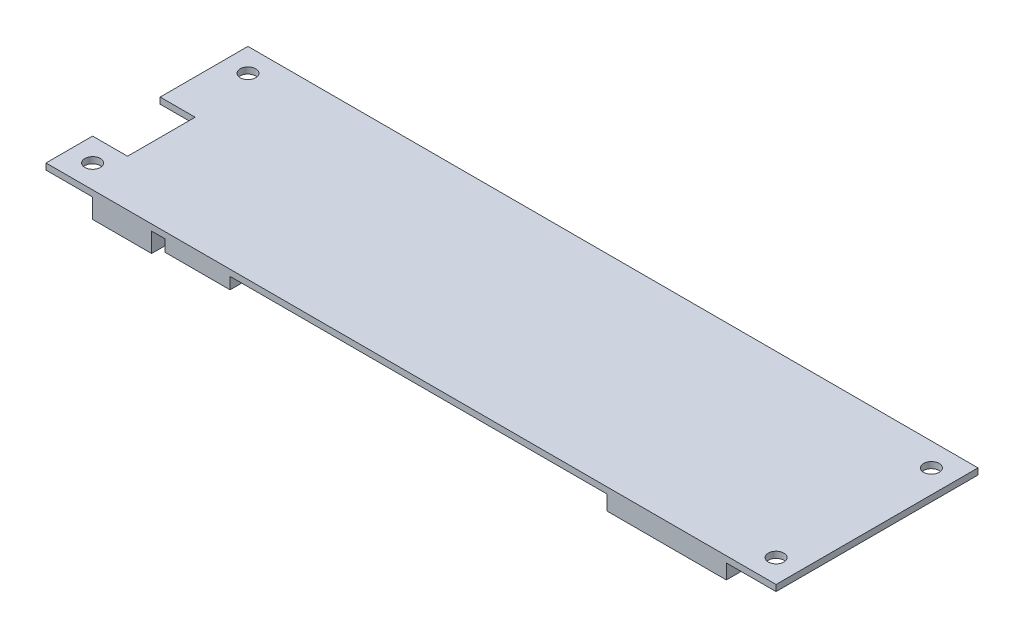
SolidWorks part; units mm, degrees
ref_plane "前视基准面" through (0, 0, 0) normal (0, 0, 1) x (1, 0, 0)
ref_plane "上视基准面" through (0, 0, 0) normal (0, 1, 0) x (1, 0, 0)
ref_plane "右视基准面" through (0, 0, 0) normal (1, 0, 0) x (0, 0, -1)
other "Configuration Table"
sketch "草图1" plane through (0, 0, 0) normal (0, 1, 0) x (1, 0, 0)
  line L1 (-47, -13) -> (47, -13)
  line L2 (-47, -13) -> (-47, 13)
  line L3 (-47, 13) -> (47, 13)
  line L4 (47, -13) -> (47, 13)
  line L5 (-47, -13) -> (47, 13) construction
  line L6 (-47, 13) -> (47, -13) construction
  circle A0 centre (-44, 10) radius 1
  circle A1 centre (-44, -10) radius 1
  circle A2 centre (44, 10) radius 1
  circle A3 centre (44, -10) radius 1
  point P0 (0, 0)
  dimension "D3" = 2
  dimension "D4" = 3
  dimension "D1" = 94
  dimension "D2" = 26
  dimension "D5" = 3
  dimension "D6" = 3
  dimension "D7" = 3
extrude "凸台-拉伸1" add sketch "草图1" along normal blind 0.8
sketch "草图2" plane through (0, 0.8, 0) normal (0, 1, 0) x (1, 0, 0)
  line L0 (-47, 13) -> (-47, -13) construction
  line L1 (-42.2, 3.9) -> (-36.7, 3.9)
  line L2 (-42.2, 3.9) -> (-42.2, -3.9)
  line L3 (-42.2, -3.9) -> (-36.7, -3.9)
  line L4 (-36.7, 3.9) -> (-36.7, -3.9)
  line L5 (40.6, 3.9) -> (46.1, 3.9)
  line L6 (40.6, 3.9) -> (40.6, -3.9)
  line L7 (40.6, -3.9) -> (46.1, -3.9)
  line L8 (46.1, 3.9) -> (46.1, -3.9)
  line L9 (47, -13) -> (47, 13) construction
  line L10 (-36.7, 0) -> (0, 0) construction
  line L11 (47, 13) -> (-47, 13) construction
  line L13 (-36.7, 10.4) -> (40.6, 10.4)
  line L14 (-36.7, 10.4) -> (-36.7, -10.4)
  line L15 (-36.7, -10.4) -> (40.6, -10.4)
  line L16 (40.6, 10.4) -> (40.6, -10.4)
  dimension "D1" = 4.8
  dimension "D2" = 0.9
  dimension "D3" = 10.3
  dimension "D4" = 9.1
  dimension "D5" = 2.6
sketch "草图3" plane through (0, 0, 0) normal (0, -1, 0) x (1, 0, 0)
  line L0 (-47, 13) -> (47, 13) construction
  line L1 (25.2, 13) -> (40.6, 13)
  line L2 (25.2, 13) -> (25.2, -2.1)
  line L3 (25.2, -2.1) -> (40.6, -2.1)
  line L4 (40.6, 13) -> (40.6, -2.1)
  line L5 (-47, -13) -> (-47, 13) construction
  line L6 (-30.7, 3.1) -> (-24, 3.1)
  line L7 (-30.7, 3.1) -> (-30.7, -3.1)
  line L8 (-30.7, -3.1) -> (-24, -3.1)
  line L9 (-24, 3.1) -> (-24, -3.1)
  line L10 (-19.425, 3.1) -> (-12.725, 3.1)
  line L11 (-19.425, 3.1) -> (-19.425, -3.1)
  line L12 (-19.425, -3.1) -> (-12.725, -3.1)
  line L13 (-12.725, 3.1) -> (-12.725, -3.1)
  line L14 (-8.15, 3.1) -> (-1.45, 3.1)
  line L15 (-8.15, 3.1) -> (-8.15, -3.1)
  line L16 (-8.15, -3.1) -> (-1.45, -3.1)
  line L17 (-1.45, 3.1) -> (-1.45, -3.1)
  line L18 (3.125, 3.1) -> (9.825, 3.1)
  line L19 (3.125, 3.1) -> (3.125, -3.1)
  line L20 (3.125, -3.1) -> (9.825, -3.1)
  line L21 (9.825, 3.1) -> (9.825, -3.1)
  line L22 (14.4, 3.1) -> (21.1, 3.1)
  line L23 (14.4, 3.1) -> (14.4, -3.1)
  line L24 (14.4, -3.1) -> (21.1, -3.1)
  line L25 (21.1, 3.1) -> (21.1, -3.1)
  line L26 (-41, 13) -> (-33.4, 13)
  line L27 (-41, 13) -> (-41, 7.1)
  line L28 (-41, 7.1) -> (-33.4, 7.1)
  line L29 (-33.4, 13) -> (-33.4, 7.1)
  line L30 (-31.7, 13) -> (-23.3, 13)
  line L31 (-31.7, 13) -> (-31.7, 7.1)
  line L32 (-31.7, 7.1) -> (-23.3, 7.1)
  line L33 (-23.3, 13) -> (-23.3, 7.1)
  line L34 (-47, 7) -> (-42.5, 7)
  line L35 (-47, 7) -> (-47, -1.7)
  line L36 (-47, -1.7) -> (-42.5, -1.7)
  line L37 (-42.5, 7) -> (-42.5, -1.7)
  line L38 (47, 13) -> (47, -13) construction
  line L39 (47, -13) -> (-47, -13) construction
  line L40 (9.825, 0) -> (14.4, 0) construction
  line L41 (-1.45, 0) -> (3.125, 0) construction
  line L42 (-12.725, 0) -> (-8.15, 0) construction
  line L43 (-24, 0) -> (-19.425, 0) construction
  line M4 (47, 13) -> (-47, 13)
  dimension "D1" = 72.2
  dimension "D2" = 6.4
  dimension "D3" = 10.9
  dimension "D4" = 25.9
  dimension "D5" = 16.3
  dimension "D6" = 9.9
  dimension "D7" = 61.4
  dimension "D8" = 15.3
  dimension "D9" = 70.3
  dimension "D10" = 20.1
  dimension "D11" = 20.1
  dimension "D12" = 6
  dimension "D13" = 80.4
  dimension "D14" = 6
  dimension "D15" = 11.3
  dimension "D16" = 4.5
extrude "凸台-拉伸4" add sketch "草图3" along normal blind 1.9 contours L3 L4 L1 L2
extrude "凸台-拉伸5" add sketch "草图3<3>" along normal blind 1 contours L8 L9 L6 L7 | L12 L13 L10 L11 | L16 L17 L14 L15 | L20 L21 L18 L19 | L24 L25 L22 L23
sketch "草图3<3>" plane through (0, 0, 0) normal (0, -1, 0) x (1, 0, 0) same geometry as "草图3"
extrude "凸台-拉伸6" add sketch "草图3<4>" along normal blind 1.5 contours L32 L33 L30 L31
sketch "草图3<4>" plane through (0, 0, 0) normal (0, -1, 0) x (1, 0, 0) same geometry as "草图3"
extrude "凸台-拉伸7" add sketch "草图3<5>" along normal blind 2.5 contours L29 L27 L28 M4 region at (-37.2, 0, 10.05)
sketch "草图3<5>" plane through (0, 0, 0) normal (0, -1, 0) x (1, 0, 0) same geometry as "草图3"
extrude "切除-拉伸1" cut sketch "草图3<6>" against normal through all contours L36 L37 L34 L35
sketch "草图3<6>" plane through (0, 0, 0) normal (0, -1, 0) x (1, 0, 0) same geometry as "草图3"
